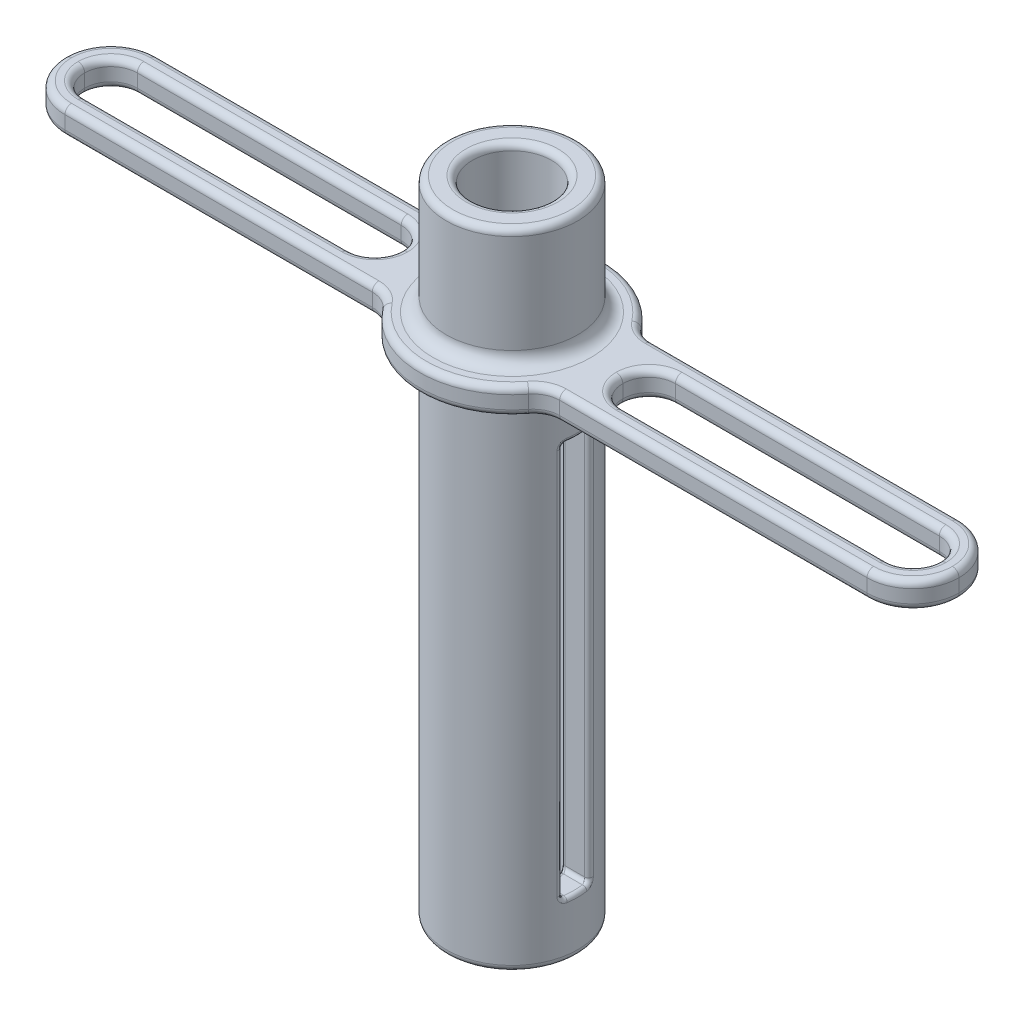
SolidWorks part; units mm, degrees
ref_plane "Front Plane" through (0, 0, 0) normal (0, 0, 1) x (1, 0, 0)
ref_plane "Top Plane" through (0, 0, 0) normal (0, 1, 0) x (1, 0, 0)
ref_plane "Right Plane" through (0, 0, 0) normal (1, 0, 0) x (0, 0, -1)
sketch "Sketch1" plane through (0, 0, 0) normal (0, 1, 0) x (1, 0, 0)
  line L0 (325, 20) -> (325, -20)
  line L1 (-340, -35) -> (340, -35)
  line L2 (-340, -35) -> (-340, 35)
  line L3 (-340, 35) -> (340, 35)
  line L4 (340, -35) -> (340, 35)
  line L5 (-340, -35) -> (340, 35) construction
  line L6 (-340, 35) -> (340, -35) construction
  line L7 (325, -20) -> (-325, -20)
  line L8 (325, -20) -> (325, 20)
  line L9 (325, 20) -> (-325, 20)
  line L10 (-325, -20) -> (-325, 20)
  line L11 (325, -20) -> (-325, 20) construction
  line L12 (325, 20) -> (-325, -20) construction
  line L13 (-325, 20) -> (-84.2692, 20)
  line L14 (-325, 20) -> (-325, -20)
  line L15 (-325, -20) -> (-84.2692, -20)
  line L16 (-84.2692, 20) -> (-84.2692, -20)
  line L17 (84.2692, -20) -> (84.2692, 20)
  line L18 (84.2692, 20) -> (325, 20)
  line L19 (325, -20) -> (84.2692, -20)
  circle A0 centre (0, 0) radius 70
  point P0 (0, 0)
  point P21 (0, 0)
  dimension "D1" = 2
extrude "Boss-Extrude1" add sketch "Sketch1" along normal blind 20 contours A0 L3 L2 L1 L7 L10 L9 | A0 L9 L16 L7 | A0 L7 L17 L9 | A0 L1 L4 L3 L9 L0 L7 | L1 A0 | L3 A0 | L1 A0 L7 | L9 A0 L3 | L7 A0 L9 region at (204.6346, 0, -22.8801) region at (76.6277, 0, 0) region at (0, 0, 0) region at (0, 0, -27.3746) region at (0, 0, 27.3746) region at (-76.6277, 0, 0) region at (-75.6756, 0, -22.8801) region at (0, 0, -49.3514) region at (0, 0, 49.3514)
sketch "Sketch2" plane through (0, 20, 0) normal (0, 1, 0) x (1, 0, 0)
  circle A0 centre (0, 0) radius 50
extrude "Boss-Extrude3" add sketch "Sketch2" along normal blind 90 and the other way blind 400 contours A0
fillet "Fillet1" radius 10 2 edges at (0, 0, 50) (0, 20, 50)
fillet "Fillet2" radius 20 4 edges at (60.6218, 10, -35) (-60.6218, 10, -35) (-60.6218, 10, 35) (60.6218, 10, 35)
fillet "Fillet3" radius 20 6 edges at (-325, 10, 20) (-325, 10, -20) (325, 10, 20) (325, 10, -20) (84.2692, 10, -20) (84.2692, 10, 20)
fillet "Fillet4" radius 35 4 edges at (-340, 10, 35) (-340, 10, -35) (340, 10, 35) (340, 10, -35)
fillet "Fillet5" radius 20 2 edges at (-84.2692, 10, 20) (-84.2692, 10, -20)
fillet "Fillet6" radius 5 26 edges at (319.1421, 20, 14.1421) (319.1421, 20, -14.1421) (204.6346, 20, -20) (90.1271, 20, -14.1421) (90.1271, 20, 14.1421) (204.6346, 20, 20) (-319.1421, 20, -14.1421) (-319.1421, 20, 14.1421) (-204.6346, 20, 20) (-90.1271, 20, 14.1421) (-90.1271, 20, -14.1421) (-204.6346, 20, -20) (-188.1195, 20, -35) (-62.4199, 20, -37.0495) (0, 20, -70) (62.4199, 20, -37.0495) (188.1195, 20, -35) (329.7487, 20, -24.7487) (329.7487, 20, 24.7487) (188.1195, 20, 35) (62.4199, 20, 37.0495) (0, 20, 70) (-62.4199, 20, 37.0495) (-188.1195, 20, 35) (-329.7487, 20, 24.7487) (-329.7487, 20, -24.7487)
fillet "Fillet7" radius 5 26 edges at (204.6346, 0, -20) (319.1421, 0, -14.1421) (319.1421, 0, 14.1421) (204.6346, 0, 20) (90.1271, 0, 14.1421) (90.1271, 0, -14.1421) (-204.6346, 0, 20) (-319.1421, 0, 14.1421) (-319.1421, 0, -14.1421) (-204.6346, 0, -20) (-90.1271, 0, -14.1421) (-90.1271, 0, 14.1421) (-62.4199, 0, 37.0495) (0, 0, 70) (62.4199, 0, 37.0495) (188.1195, 0, 35) (329.7487, 0, 24.7487) (329.7487, 0, -24.7487) (188.1195, 0, -35) (62.4199, 0, -37.0495) (0, 0, -70) (-62.4199, 0, -37.0495) (-188.1195, 0, -35) (-329.7487, 0, -24.7487) (-329.7487, 0, 24.7487) (-188.1195, 0, 35)
sketch "Sketch3" plane through (0, -380, 0) normal (0, -1, 0) x (1, 0, 0)
  circle A0 centre (0, 0) radius 30
extrude "Cut-Extrude1" cut sketch "Sketch3" against normal blind 527
fillet "Fillet8" radius 5 2 edges at (0, 110, 50) (0, 110, 30)
fillet "Fillet9" radius 5 2 edges at (0, -380, 50) (0, -380, -30)
sketch "Sketch5" plane through (0, 0, 0) normal (1, 0, 0) x (0, 0, -1)
  line L0 (0, -375) -> (0, 0)
  line L1 (-50, -375) -> (50, -375) construction
  line L11 (-10, -337.5) -> (10, -337.5)
  line L12 (-10, -337.5) -> (-10, -37.5)
  line L13 (-10, -37.5) -> (10, -37.5)
  line L14 (10, -337.5) -> (10, -37.5)
  line L15 (-10, -337.5) -> (10, -37.5) construction
  line L16 (-10, -37.5) -> (10, -337.5) construction
  point P5 (0, -187.5)
  point P7 (0, -187.5)
extrude "Cut-Extrude3" cut sketch "Sketch5" against normal blind 78 and the other way blind 78 contours L11 L14 L13 L0 | L13 L12 L11 L0 region at (0, -187.5, 5) region at (0, -187.5, -5)
fillet "Fillet11" radius 3 24 edges at (-50, -337.5, 0) (-30, -337.5, 0) (-48.9898, -187.5, -10) (-28.2843, -187.5, -10) (-38.637, -337.5, -10) (-30, -37.5, 0) (-38.637, -37.5, -10) (-50, -37.5, 0) (-38.637, -337.5, 10) (-28.2843, -187.5, 10) (-38.637, -37.5, 10) (-48.9898, -187.5, 10) (48.9898, -187.5, -10) (28.2843, -187.5, -10) (50, -337.5, 0) (30, -337.5, 0) (38.637, -337.5, -10) (38.637, -37.5, -10) (30, -37.5, 0) (50, -37.5, 0) (38.637, -37.5, 10) (28.2843, -187.5, 10) (38.637, -337.5, 10) (48.9898, -187.5, 10)
